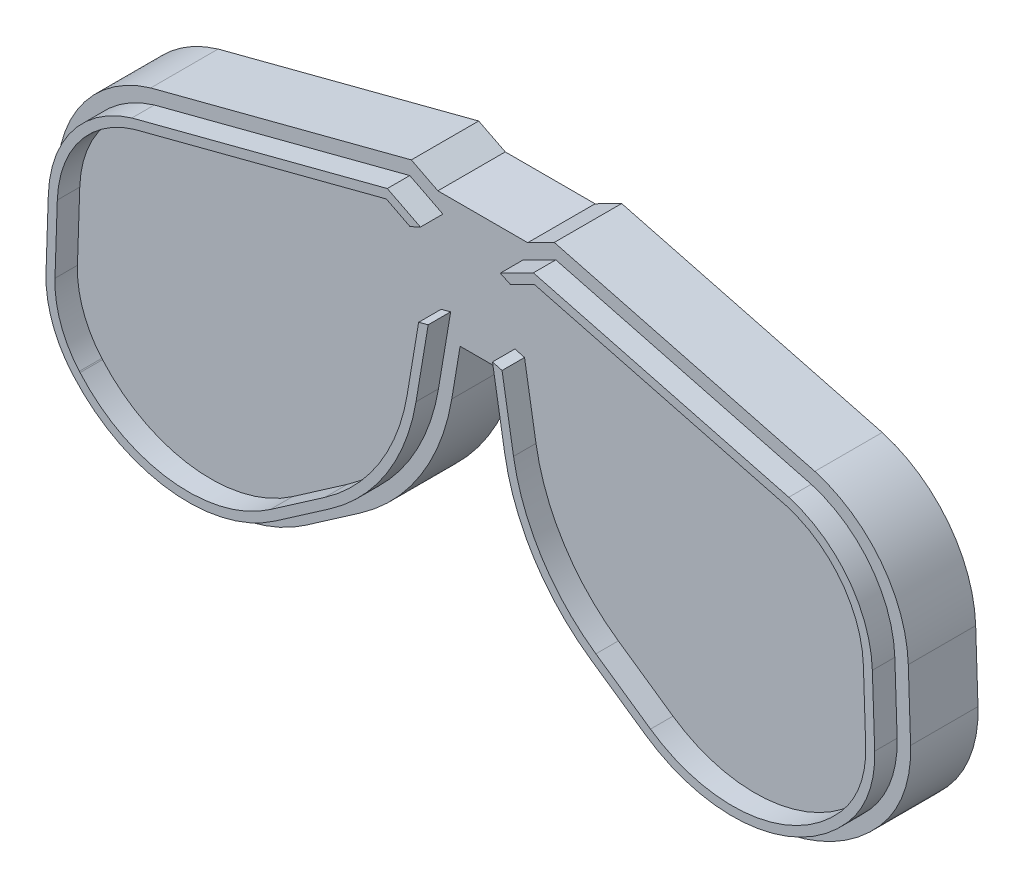
SolidWorks part; units mm, degrees
ref_plane "Front Plane" through (0, 0, 0) normal (0, 0, 1) x (1, 0, 0)
ref_plane "Top Plane" through (0, 0, 0) normal (0, 1, 0) x (1, 0, 0)
ref_plane "Right Plane" through (0, 0, 0) normal (1, 0, 0) x (0, 0, -1)
sketch "Sketch2" plane through (0, 0, 0) normal (0, 0, 1) x (1, 0, 0)
  line L0 (77.6667, 150) -> (388.3333, 150) construction
  line L9 (13.6071, 110.9778) -> (13.2123, 111.4293)
  line L10 (-3.7003, 158.8773) -> (-2.3893, 197.8301)
  line L11 (50.44, 266.0177) -> (197.7702, 304.4461)
  line L12 (197.7702, 304.4461) -> (212.7827, 296.8135)
  line L14 (225.3527, 226.994) -> (220.6363, 198.7801)
  line L15 (168.7902, 117.0169) -> (137.902, 95.603)
  line L23 (212.7827, 296.8135) -> (263.5827, 296.8135)
  line L27 (238.1827, 226.994) -> (238.1827, 83.3839) construction
  line L29 (238.1827, 296.8135) -> (238.1827, 354.7702) construction
  line L31 (278.5953, 304.4461) -> (263.5827, 296.8135)
  line L32 (425.9254, 266.0177) -> (278.5953, 304.4461)
  line L34 (251.0128, 226.994) -> (255.7292, 198.7801)
  line L35 (480.0658, 158.8773) -> (478.7547, 197.8301)
  line L36 (462.7584, 110.9778) -> (463.1531, 111.4293)
  line L37 (307.5753, 117.0169) -> (338.4634, 95.603)
  line L38 (225.3527, 226.994) -> (251.0128, 226.994)
  line L39 (23.1679, 119.3372) -> (22.7732, 119.7887)
  line L40 (8.9925, 158.4501) -> (10.3036, 197.4029)
  line L41 (53.8447, 253.7808) -> (196.3113, 290.9407)
  line L42 (196.3113, 290.9407) -> (209.7396, 284.1135)
  line L51 (214.5994, 239.694) -> (208.1101, 200.874)
  line L52 (161.5544, 127.454) -> (130.6662, 106.0401)
  line L71 (52.4805, 258.675) -> (196.8948, 296.3428)
  line L72 (209.7396, 284.1135) -> (266.6258, 284.1135) construction
  line L75 (214.5994, 239.694) -> (261.766, 239.694) construction
  line L76 (196.8948, 296.3428) -> (215.6134, 286.826)
  line L85 (219.9982, 241.1793) -> (213.1205, 200.0364)
  line L86 (164.4487, 123.2792) -> (133.5605, 101.8652)
  line L87 (19.3436, 115.9934) -> (18.9488, 116.4449)
  line L88 (3.9153, 158.621) -> (5.2264, 197.5738)
  line L89 (56.5839, 243.9954) -> (195.1442, 280.1363) construction
  line L90 (19.1467, 158.1083) -> (20.4578, 197.0611) construction
  line L91 (155.7658, 135.8037) -> (124.8776, 114.3898) construction
  line L92 (207.0943, 256.4193) -> (198.0891, 202.5492) construction
  line L93 (207.0943, 256.4193) -> (219.9982, 241.1793) construction
  line L94 (195.1442, 280.1363) -> (211.9617, 271.586) construction
  line L95 (211.9617, 271.586) -> (215.6134, 286.826) construction
  line L96 (195.7277, 285.5385) -> (208.5224, 279.0335) construction
  line L97 (208.5224, 279.0335) -> (209.7396, 284.1135) construction
  line L98 (55.2123, 248.8876) -> (195.7277, 285.5385) construction
  line L99 (14.0696, 158.2792) -> (15.3807, 197.232) construction
  line L100 (158.6601, 131.6289) -> (127.7719, 110.2149) construction
  line L101 (210.2981, 244.774) -> (203.0996, 201.7116) construction
  line L102 (210.2981, 244.774) -> (214.5994, 239.694) construction
  line L103 (209.7396, 284.1135) -> (215.6134, 286.826)
  line L104 (214.5994, 239.694) -> (219.9982, 241.1793)
  line L105 (261.766, 239.694) -> (268.2554, 200.874)
  line L106 (422.5208, 253.7808) -> (280.0542, 290.9407) construction
  line L109 (280.0542, 290.9407) -> (266.6258, 284.1135) construction
  line L111 (261.766, 239.694) -> (268.2554, 200.874) construction
  line L113 (314.811, 127.454) -> (345.6992, 106.0401) construction
  line L115 (467.373, 158.4501) -> (466.0619, 197.4029) construction
  line L117 (453.1975, 119.3372) -> (453.5923, 119.7887) construction
  line L118 (314.811, 127.454) -> (345.6992, 106.0401)
  line L119 (453.1975, 119.3372) -> (453.5923, 119.7887)
  line L120 (467.373, 158.4501) -> (466.0619, 197.4029)
  line L121 (422.5208, 253.7808) -> (280.0542, 290.9407)
  line L122 (280.0542, 290.9407) -> (266.6258, 284.1135)
  line L123 (266.6258, 284.1135) -> (260.752, 286.826)
  line L124 (279.4706, 296.3428) -> (260.752, 286.826)
  line L125 (423.8849, 258.675) -> (279.4706, 296.3428)
  line L126 (472.4501, 158.621) -> (471.139, 197.5738)
  line L127 (457.0219, 115.9934) -> (457.4166, 116.4449)
  line L128 (311.9167, 123.2792) -> (342.8049, 101.8652)
  line L129 (256.3672, 241.1793) -> (263.2449, 200.0364)
  line L130 (261.766, 239.694) -> (256.3672, 241.1793)
  line L131 (30.8166, 126.0248) -> (30.4218, 126.4763) construction
  line L132 (26.9923, 122.681) -> (26.5975, 123.1325) construction
  arc A5 (137.902, 95.603) -> (13.6071, 110.9778) centre (84.3573, 172.8377) cw
  arc A6 (13.2123, 111.4293) -> (-3.7003, 158.8773) centre (64.8408, 156.5703) cw
  arc A7 (50.44, 266.0177) -> (-2.3893, 197.8301) centre (71.2291, 195.3522) ccw
  arc A9 (220.6363, 198.7801) -> (168.7902, 117.0169) centre (97.8796, 219.3007) cw
  arc A16 (255.7292, 198.7801) -> (307.5753, 117.0169) centre (378.4858, 219.3007) ccw
  arc A17 (425.9254, 266.0177) -> (478.7547, 197.8301) centre (405.1364, 195.3522) cw
  arc A18 (463.1531, 111.4293) -> (480.0658, 158.8773) centre (411.5246, 156.5703) ccw
  arc A19 (338.4634, 95.603) -> (462.7584, 110.9778) centre (392.0082, 172.8377) ccw
  arc A20 (130.6662, 106.0401) -> (23.1679, 119.3372) centre (84.3573, 172.8377) cw
  arc A21 (22.7732, 119.7887) -> (8.9925, 158.4501) centre (64.8408, 156.5703) cw
  arc A22 (53.8447, 253.7808) -> (10.3036, 197.4029) centre (71.2291, 195.3522) ccw
  arc A27 (208.1101, 200.874) -> (161.5544, 127.454) centre (97.8796, 219.3007) cw
  arc A40 (213.1205, 200.0364) -> (164.4487, 123.2792) centre (97.8796, 219.3007) cw
  arc A41 (133.5605, 101.8652) -> (19.3436, 115.9934) centre (84.3573, 172.8377) cw
  arc A42 (18.9488, 116.4449) -> (3.9153, 158.621) centre (64.8408, 156.5703) cw
  arc A43 (52.4805, 258.675) -> (5.2264, 197.5738) centre (71.2291, 195.3522) ccw
  arc A44 (56.5839, 243.9954) -> (20.4578, 197.0611) centre (71.2291, 195.3522) ccw construction
  arc A45 (30.4218, 126.4763) -> (19.1467, 158.1083) centre (64.8408, 156.5703) cw construction
  arc A46 (124.8776, 114.3898) -> (30.8166, 126.0248) centre (84.3573, 172.8377) cw construction
  arc A47 (198.0891, 202.5492) -> (155.7658, 135.8037) centre (97.8796, 219.3007) cw construction
  arc A48 (55.2123, 248.8876) -> (15.3807, 197.232) centre (71.2291, 195.3522) ccw construction
  arc A49 (26.5975, 123.1325) -> (14.0696, 158.2792) centre (64.8408, 156.5703) cw construction
  arc A50 (127.7719, 110.2149) -> (26.9923, 122.681) centre (84.3573, 172.8377) cw construction
  arc A51 (203.0996, 201.7116) -> (158.6601, 131.6289) centre (97.8796, 219.3007) cw construction
  arc A53 (268.2554, 200.874) -> (314.811, 127.454) centre (378.4858, 219.3007) ccw construction
  arc A55 (345.6992, 106.0401) -> (453.1975, 119.3372) centre (392.0082, 172.8377) ccw construction
  arc A57 (453.5923, 119.7887) -> (467.373, 158.4501) centre (411.5246, 156.5703) ccw construction
  arc A59 (422.5208, 253.7808) -> (466.0619, 197.4029) centre (405.1364, 195.3522) cw construction
  arc A60 (268.2554, 200.874) -> (314.811, 127.454) centre (378.4858, 219.3007) ccw
  arc A61 (345.6992, 106.0401) -> (453.1975, 119.3372) centre (392.0082, 172.8377) ccw
  arc A62 (453.5923, 119.7887) -> (467.373, 158.4501) centre (411.5246, 156.5703) ccw
  arc A63 (422.5208, 253.7808) -> (466.0619, 197.4029) centre (405.1364, 195.3522) cw
  arc A64 (423.8849, 258.675) -> (471.139, 197.5738) centre (405.1364, 195.3522) cw
  arc A65 (457.4166, 116.4449) -> (472.4501, 158.621) centre (411.5246, 156.5703) ccw
  arc A66 (342.8049, 101.8652) -> (457.0219, 115.9934) centre (392.0082, 172.8377) ccw
  arc A67 (263.2449, 200.0364) -> (311.9167, 123.2792) centre (378.4858, 219.3007) ccw
  dimension "D1" = 50.8
  dimension "D2" = 12.7
  dimension "D4" = 147.2331
  dimension "D5" = 5.08
  dimension "D6" = 149.246
extrude "Boss-Extrude4" add sketch "Sketch2" along normal blind 12.7 contours L129 A67 L128 A66 L127 A65 L126 A64 L125 L124 L123 L122 L121 A63 L120 A62 L119 A61 L118 A60 L105 L130 | L71 L76 L103 L42 L41 A22 L40 A21 L39 A20 L52 A27 L51 L104 L85 A40 L86 A41 L87 A42 L88 A43 region at (262.0395, 219.7873, 0)
extrude "Boss-Extrude5" add sketch "Sketch2<7>" against normal blind 38.1 separate body contours L37 A19 L36 A18 L35 A17 L32 L31 L23 L12 L11 A7 L10 A6 L9 A5 L15 A9 L14 L38 L34 A16 A67 L129 L130 L105 A60 L118 A61 L119 A62 L120 A63 L121 L122 L123 L124 L125 A64 L126 A65 L127 A66 L128 A43 L71 L76 L103 L42 | A22 L40 A21 L39 A20 L52 A27 L51 L104 L85 A40 L86 A41 L87 A42 L88 A43 L71 L76 L103 L42 L41 | A60 L118 A61 L119 A62 L120 A63 L121 L122 L123 L124 L125 A64 L126 A65 L127 A66 L128 A67 L129 L130 L105 region at (17.4286, 114.7174, 0)
sketch "Sketch2<7>" plane through (0, 0, 0) normal (0, 0, 1) x (1, 0, 0) same geometry as "Sketch2"
